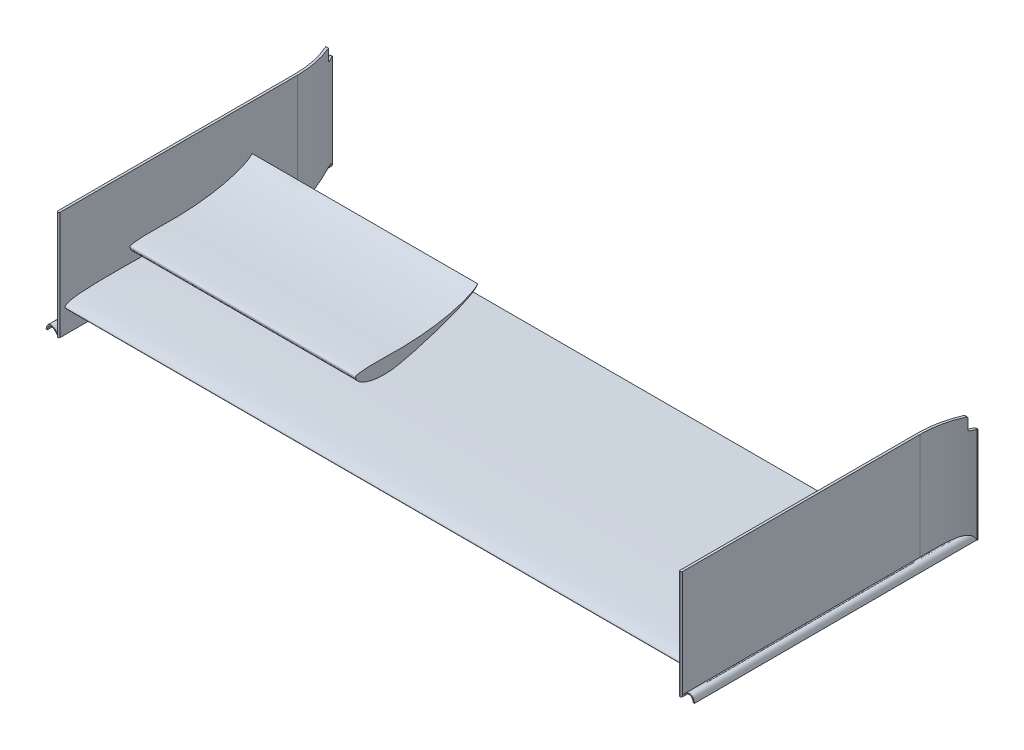
SolidWorks part; units mm, degrees
other "Markup1"
sketch "Sketch8" plane through (689.61, 321.434, 0) normal (0.4886, 0.11, -0.8656) x (-0.8712, 0.0061, -0.491)
ref_plane "Front Plane" through (0, 0, 0) normal (0, 0, 1) x (1, 0, 0)
ref_plane "Top Plane" through (0, 0, 0) normal (0, 1, 0) x (1, 0, 0)
ref_plane "Center Plane" through (0, 0, 0) normal (1, 0, 0) x (0, 0, -1)
ref_plane "Front Limit" through (0, 0, 1702.0819) normal (0, 0, 1) x (1, 0, 0)
ref_plane "Right Limit" through (-711.2, 0, 0) normal (1, 0, 0) x (0, 0, -1)
ref_plane "Left Limit" through (711.2, 0, 0) normal (1, 0, 0) x (0, 0, -1)
ref_plane "Rear Limit Outside Inner Wheel Plane" through (0, 0, 1077.0819) normal (0, 0, 1) x (1, 0, 0)
ref_plane "Lower Limit" through (0, 0, 0) normal (0, 1, 0) x (1, 0, 0)
ref_plane "Upper Limit Outside Inner Wheel Plane" through (0, 250, 0) normal (0, 1, 0) x (1, 0, 0)
ref_plane "Right Tower Outer Limit" through (-502.92, 0, 0) normal (1, 0, 0) x (0, 0, -1)
ref_plane "Left Tower Outer Limit" through (502.92, 0, 0) normal (1, 0, 0) x (0, 0, -1)
ref_plane "Upper Limit" through (0, 500, 0) normal (0, 1, 0) x (1, 0, 0)
ref_plane "Wing Right Edge" through (-676.91, 0, 0) normal (1, 0, 0) x (0, 0, -1)
ref_plane "Endplate Clearance" through (0, 12.7, 0) normal (0, 1, 0) x (1, 0, 0)
ref_plane "Tower Left Edge" through (-285.75, 0, 0) normal (1, 0, 0) x (0, 0, -1)
ref_plane "Tower Right Edge" through (-479.552, 0, 0) normal (1, 0, 0) x (0, 0, -1)
ref_plane "Tower Mid-Plane" through (-382.651, 0, 0) normal (1, 0, 0) x (0, 0, -1)
sketch "Sketch13" plane through (0, 12.7, 0) normal (0, 1, 0) x (1, 0, 0)
  line L0 (-681.749, -1702.0819) -> (-748.5505, -1702.0819) construction
  line L3 (-338.2945, -1702.0819) -> (338.2945, -1702.0819) construction
  line L4 (-1656.8005, -1077.0819) -> (-1116.8551, -1077.0819) construction
  line L5 (-339.8221, -1077.0819) -> (339.8221, -1077.0819) construction
  line L6 (-711.2, -238.9653) -> (-711.2, 238.9653) construction
  line L9 (1249.6701, -1702.0819) -> (1297.5169, -1702.0819) construction
  line L10 (-692.8302, -1081.9916) -> (-688.3642, -1079.5705) construction
  line L11 (-704.7698, 2304.2869) -> (-704.7698, 1682.8955) construction
  line L12 (-698.5, -2427.286) -> (-698.5, -1932.9922) construction
  line L13 (-711.2, 1331.8621) -> (-711.2, 2114.8601) construction
  line L14 (-663.1866, -1178.8382) -> (-663.1866, -1686.8457)
  line L15 (-668.2666, -1686.8382) -> (-668.2666, -1178.8382)
  arc A6 (-663.1866, -1686.8457) -> (-668.2666, -1686.8382) centre (-665.7266, -1686.8419) cw
  arc A7 (-668.2666, -1178.8382) -> (-692.8302, -1081.9916) centre (-871.4666, -1178.8382) ccw
  arc A8 (-663.1866, -1178.8382) -> (-688.3642, -1079.5705) centre (-871.4666, -1178.8382) ccw
  arc A9 (-668.2666, -1178.8382) -> (-675.6742, -1124.4731) centre (-871.4666, -1178.8382) ccw construction
  arc A12 (-663.1866, -1178.8382) -> (-670.7794, -1123.114) centre (-871.4666, -1178.8382) ccw construction
  arc A13 (-688.3642, -1079.5705) -> (-692.8302, -1081.9916) centre (-690.5972, -1080.781) ccw
  point P7 (-665.7303, -1689.3819)
  point P8 (-698.5, -1702.0819)
  point P10 (-681.749, -1702.0819)
  point P17 (-704.85, -1089.7819)
  point P32 (-692.8302, -1081.9916)
  dimension "D5" = 2.54
  dimension "D9" = 203.2
  dimension "D1" = 12.7
  dimension "D3" = 12.7
  dimension "D4" = 5.08
  dimension "D6" = 508
  dimension "D8" = 60.4668
  dimension "D7" = 5.08
ref_plane "Right Tower Outer Edge" through (-496.57, 0, 0) normal (1, 0, 0) x (0, 0, -1)
ref_plane "Footplate Front Plane" through (0, 0, 1686.8419) normal (0, 0, 1) x (1, 0, 0)
extrude "Endplate" add sketch "Sketch13" along normal offset from surface (232.22 mm away) 5.08 contours L14 A6 L15 A7 A13 A8 up to plane "Upper Limit Outside Inner Wheel Plane"
sketch "Sketch9" plane through (0, 0, 0) normal (1, 0, 0) x (0, 0, -1)
  line L0 (-1689.3819, 6.2912) -> (-1689.3819, -13.0537) construction
  line L2 (423.3132, 0) -> (-423.3132, 0) construction
  line L3 (-1219.5516, 71.4792) -> (-1219.5392, 70.7113)
  line L4 (-1689.3819, 101.5557) -> (-1689.3819, 173.1029) construction
  line L5 (-1945.3823, 0) -> (-1740.2495, 0) construction
  line L10 (-1219.5516, 71.4792) -> (-1676.6819, 63.5) construction
  line L12 (-1676.6819, 63.5) -> (-1677.5512, 113.3019) construction
  spline S1 degree 3 poles (-1219.5392, 70.7113) (-1227.0861, 69.3984) (-1242.1864, 66.7717) (-1272.4544, 61.9112) (-1310.3806, 56.4182) (-1356, 50.7244) (-1401.7138, 45.9542) (-1447.5115, 42.2303) (-1493.4584, 39.5613) (-1531.8694, 38.8064) (-1562.6614, 39.5041) (-1585.7469, 40.7463) (-1608.8067, 42.8266) (-1627.9542, 45.4527) (-1643.2157, 48.362) (-1654.6407, 50.922) (-1664.1956, 54.4343) (-1671.8661, 57.2292) (-1679.7108, 64.0181) (-1670.8486, 69.3187) (-1662.9781, 71.2102) (-1653.0354, 72.9214) (-1641.5607, 74.0215) (-1626.2817, 75.0131) (-1607.2992, 75.6384) (-1584.5621, 75.8826) (-1561.8863, 75.857) (-1531.6907, 75.6204) (-1493.8655, 75.2452) (-1448.3868, 74.7043) (-1402.7761, 73.923) (-1357.1, 73.1795) (-1311.3437, 72.5052) (-1273.1582, 72.0528) (-1242.5505, 71.714) (-1227.2239, 71.5576) (-1219.5516, 71.4792) knots 0 0 0 0 0.02488 0.049781 0.099567 0.14934 0.199092 0.248839 0.298568 0.348561 0.373567 0.398591 0.423638 0.448742 0.461353 0.474029 0.486955 0.493558 0.502381 0.511191 0.517824 0.530564 0.54309 0.555505 0.580209 0.604805 0.629344 0.653862 0.702881 0.752206 0.801586 0.851045 0.900581 0.950217 0.975079 1 1 1 1
  dimension "D1" = 25.4
  dimension "D2" = 1
  dimension "D3" = 63.5
  dimension "D6" = 457.2
extrude "Boss-Extrude1" add sketch "Sketch9" against normal up to next contours S1 L3
ref_plane "Plane3" through (-2.4764, 0, 1687.8151) normal (-0.0015, 0, 1) x (1, 0, 0.0015)
sketch "Sketch10" plane through (-496.57, 0, 0) normal (1, 0, 0) x (0, 0, -1)
  line L7 (-1253.0024, 45.6286) -> (-1162.2541, 41.8604) construction
  line L15 (-1451.2356, 51.0549) -> (-1480.3015, 75.0777)
  line L16 (-1354.4791, 51.0549) -> (-1451.2356, 51.0549)
  line L19 (-1253.0024, 45.6286) -> (-1354.4791, 51.0549)
  line L21 (-1075.0863, 331.2535) -> (-1041.2474, 331.2535)
  line L24 (-1162.2541, 41.8604) -> (-1108.1928, 92.3259) construction
  line L25 (-1108.1928, 92.3259) -> (-1073.6675, 134.2437) construction
  line L26 (-1073.6675, 134.2437) -> (-1063.3396, 228.2149) construction
  line L27 (-1063.3396, 228.2149) -> (-1031.4549, 293.1063) construction
  line L28 (423.3132, 0) -> (-423.3132, 0) construction
  line L29 (-1077.0819, 339.8221) -> (-1077.0819, -339.8221) construction
  line L30 (-1219.5516, 71.4792) -> (-1219.5516, -47.0525) construction
  line L31 (-1688.4184, 71.4792) -> (-1416.5181, 71.4792) construction
  line L32 (-1219.5392, 70.7113) -> (-1219.5516, 71.4792)
  line L33 (-1219.5392, 70.7113) -> (-1219.5516, 71.4792)
  line L34 (-1038.7074, 299.3065) -> (-1038.7074, 328.7135)
  line L35 (-1036.1674, 296.7665) -> (-1033.7345, 296.7665)
  line L37 (-1178.8382, 244.92) -> (-1686.8457, 244.92) construction
  line L38 (-1075.0863, 331.2535) -> (-1097.159, 330.9939)
  circle A11 centre (-798.8819, 203.2) radius 203.2 construction
  arc A14 (-1036.1674, 296.7665) -> (-1038.7074, 299.3065) centre (-1036.1674, 299.3065) cw
  arc A15 (-1031.4549, 293.1063) -> (-1033.7345, 296.7665) centre (-1033.7345, 294.2265) ccw
  arc A16 (-1041.2474, 331.2535) -> (-1038.7074, 328.7135) centre (-1041.2474, 328.7135) cw
  spline_without_curve S0
  spline S1 degree 3 poles (-1097.159, 330.9939) (-1148.9166, 330.128) (-1194.764, 314.059) (-1331.7956, 204.3697) (-1393.3764, 127.2338) (-1480.3015, 75.0777) knots 0 0 0 0 0.231496 0.433154 1 1 1 1
  spline S3 degree 3 poles (-1219.5392, 70.7113) (-1227.0861, 69.3984) (-1242.1864, 66.7717) (-1272.4544, 61.9112) (-1310.3806, 56.4182) (-1356, 50.7244) (-1401.7138, 45.9542) (-1447.5115, 42.2303) (-1493.4584, 39.5613) (-1531.8694, 38.8064) (-1562.6614, 39.5041) (-1585.7469, 40.7463) (-1608.8067, 42.8266) (-1627.9542, 45.4527) (-1643.2157, 48.362) (-1654.6407, 50.922) (-1664.1956, 54.4343) (-1671.8661, 57.2292) (-1679.7108, 64.0181) (-1670.8486, 69.3187) (-1662.9781, 71.2102) (-1653.0354, 72.9214) (-1641.5607, 74.0215) (-1626.2817, 75.0131) (-1607.2992, 75.6384) (-1584.5621, 75.8826) (-1561.8863, 75.857) (-1531.6907, 75.6204) (-1493.8655, 75.2452) (-1448.3868, 74.7043) (-1402.7761, 73.923) (-1357.1, 73.1795) (-1311.3437, 72.5052) (-1273.1582, 72.0528) (-1242.5505, 71.714) (-1227.2239, 71.5576) (-1219.5516, 71.4792) knots 0 0 0 0 0.02488 0.049781 0.099567 0.14934 0.199092 0.248839 0.298568 0.348561 0.373567 0.398591 0.423638 0.448742 0.461353 0.474029 0.486955 0.493558 0.502381 0.511191 0.517824 0.530564 0.54309 0.555505 0.580209 0.604805 0.629344 0.653862 0.702881 0.752206 0.801586 0.851045 0.900581 0.950217 0.975079 1 1 1 1 construction
  spline S4 degree 3 poles (698.5236, -1924.2144) (65.8834, 81.8124) (-596.1286, 64.5596) (-1273.1582, 72.0528) (-1311.3437, 72.5052) (-1357.1, 73.1795) (-1402.7761, 73.923) (-1448.3868, 74.7043) (-1493.8655, 75.2452) (-1531.6907, 75.6204) (-1561.8863, 75.857) (-1584.5621, 75.8826) (-1607.2992, 75.6384) (-1626.2817, 75.0131) (-1641.5607, 74.0215) (-1653.0354, 72.9214) (-1662.9781, 71.2102) (-1670.8486, 69.3187) (-1679.7108, 64.0181) (-1671.8661, 57.2292) (-1664.1956, 54.4343) (-1654.6407, 50.922) (-1643.2157, 48.362) (-1627.9542, 45.4527) (-1608.8067, 42.8266) (-1585.7469, 40.7463) (-1562.6614, 39.5041) (-1531.8694, 38.8064) (-1493.4584, 39.5613) (-1447.5115, 42.2303) (-1401.7138, 45.9542) (-1356, 50.7244) (-1310.3806, 56.4182) (-1272.4544, 61.9112) (-952.6642, 113.2634) (-661.4362, 241.8766) (111.3217, -2533.5152) knots -2.09969 -2.09969 -2.09969 -2.09969 0.024921 0.049783 0.099419 0.148955 0.198414 0.247794 0.297119 0.346138 0.370656 0.395195 0.419791 0.444495 0.45691 0.469436 0.482176 0.488809 0.497619 0.506442 0.513045 0.525971 0.538647 0.551258 0.576362 0.601409 0.626433 0.651439 0.701432 0.751161 0.800908 0.85066 0.900433 0.950219 0.97512 1.952384 1.952384 1.952384 1.952384 only from (-1219.5516, 71.4792) to (-1219.5392, 70.7113)
  spline S5 degree 3 poles (-1219.5516, 71.4792) (-1227.2239, 71.5576) (-1242.5505, 71.714) (-1273.1582, 72.0528) (-1311.3437, 72.5052) (-1357.1, 73.1795) (-1402.7761, 73.923) (-1448.3868, 74.7043) (-1493.8655, 75.2452) (-1531.6907, 75.6204) (-1561.8863, 75.857) (-1584.5621, 75.8826) (-1607.2992, 75.6384) (-1626.2817, 75.0131) (-1641.5607, 74.0215) (-1653.0354, 72.9214) (-1662.9781, 71.2102) (-1670.8486, 69.3187) (-1679.7108, 64.0181) (-1671.8661, 57.2292) (-1664.1956, 54.4343) (-1654.6407, 50.922) (-1643.2157, 48.362) (-1627.9542, 45.4527) (-1608.8067, 42.8266) (-1585.7469, 40.7463) (-1562.6614, 39.5041) (-1531.8694, 38.8064) (-1493.4584, 39.5613) (-1447.5115, 42.2303) (-1401.7138, 45.9542) (-1356, 50.7244) (-1310.3806, 56.4182) (-1272.4544, 61.9112) (-1242.1864, 66.7717) (-1227.0861, 69.3984) (-1219.5392, 70.7113) knots 0 0 0 0 0.024921 0.049783 0.099419 0.148955 0.198414 0.247794 0.297119 0.346138 0.370656 0.395195 0.419791 0.444495 0.45691 0.469436 0.482176 0.488809 0.497619 0.506442 0.513045 0.525971 0.538647 0.551258 0.576362 0.601409 0.626433 0.651439 0.701432 0.751161 0.800908 0.85066 0.900433 0.950219 0.97512 1 1 1 1 construction
  point P0 (-901.0423, 453.0659)
  point P1 (-1057.5185, 453.0659)
  point P6 (-1172.7675, 276.2638)
  point P49 (-1213.8243, 119.2502)
  dimension "D3" = 406.4
  dimension "D4" = 278.2
  dimension "D1" = 2.54
  dimension "D6" = 2.54
  dimension "D7" = 2.54
  dimension "D5" = 0
sketch "Sketch29" plane through (-2.4764, 0, 1687.8151) normal (-0.0015, 0, 1) x (1, 0, 0.0015)
  line L0 (-691.2419, 13.171) -> (-688.7459, 12.7)
  line L1 (-663.8777, 14.3707) -> (-665.7909, 12.7)
  line L2 (-691.2419, 244.92) -> (-691.2419, 12.7) construction
  line L3 (-691.2419, 12.7) -> (-666.5362, 12.7) construction
  spline S0 degree 2 poles (-665.7909, 12.7) (-684.6668, 34.3152) (-688.7459, 12.7) knots 0 0 0 1 1 1
  spline S1 degree 1 poles (-663.8777, 14.3707) (-691.2419, 13.171) knots 0 0 1 1 construction
  spline S2 degree 2 poles (-663.8777, 14.3707) (-667.5007, 18.5279) (-672.8595, 23.0348) (-676.4087, 25.0689) (-678.9321, 25.8712) (-680.9696, 26.1076) (-682.991, 25.8639) (-684.8805, 25.1037) (-686.5179, 23.8905) (-688.2115, 21.9339) (-690.4596, 17.446) (-691.2419, 13.171) knots 0 0 0 0.1875 0.3125 0.40625 0.46875 0.53125 0.59375 0.65625 0.71875 0.8125 1 1 1
  dimension "D1" = 2.54
extrude "Boss-Extrude8" add sketch "Sketch29" against normal up to body
sketch "Sketch30" plane through (-2.4764, 0, 1687.8151) normal (-0.0015, 0, 1) x (1, 0, 0.0015)
  line L0 (-688.7459, 12.7) -> (-665.7909, 12.7)
  parabola Q0 (-688.7459, 12.7) -> (-665.7909, 12.7) focus (-681.9012, 20.7799) apex (-682.7369, 23.2216) construction
  parabola Q1 (-688.7459, 12.7) -> (-665.7909, 12.7) focus (-681.9012, 20.7799) apex (-682.7369, 23.2216) construction
  parabola Q2 (-688.7459, 12.7) -> (-665.7909, 12.7) focus (-681.9012, 20.7799) apex (-682.7369, 23.2216) construction
  spline S0 degree 2 poles (-688.7459, 12.7) (-682.9378, 35.0777) (-665.7909, 12.7) knots 0 0 0 1 1 1
extrude "Cut-Extrude1" cut sketch "Sketch30" against normal through all separate body
mirror "Mirror2" about plane through (0, 0, 0) normal (1, 0, 0) of bodies 141 120 117
move or copy body "Body-Move/Copy1" bodies to move or copy 121 copy no translate (0, -322.326, 19.8438) parameters "D1"=0, "D2"=322.326, "D3"=19.8438
ref_plane "Endplate Edge" through (-663.1866, 0, 0) normal (1, 0, 0) x (0, 0, -1)
curve "Curve1"
  spline degree 3 poles (0, -0.6596, 253.0171) (0, 0.164, 254.2303) (0, -0.6286, 253.1665) (0, -1.3215, 252.4604) (0, -2.7687, 250.8924) (0, -4.3082, 249.0425) (0, -5.8603, 246.5121) (0, -7.3644, 243.3654) (0, -8.9341, 239.5667) (0, -10.5476, 235.1217) (0, -12.1934, 230.0511) (0, -13.8573, 224.3813) (0, -15.5314, 218.144) (0, -17.2004, 211.3736) (0, -18.8523, 204.109) (0, -20.4766, 196.3935) (0, -22.065, 188.2741) (0, -23.5981, 179.7984) (0, -25.0735, 171.0197) (0, -26.4724, 161.9885) (0, -27.7973, 152.7634) (0, -29.0379, 143.4034) (0, -30.1902, 133.9763) (0, -31.2623, 124.5575) (0, -32.2271, 115.225) (0, -33.0667, 106.0547) (0, -33.7337, 97.1112) (0, -34.1925, 88.4456) (0, -34.3907, 80.1061) (0, -34.3696, 72.1354) (0, -33.9793, 64.5483) (0, -33.1884, 57.342) (0, -32.0701, 50.4871) (0, -30.6214, 43.9819) (0, -28.9226, 37.8331) (0, -27.0037, 32.0668) (0, -24.9097, 26.7074) (0, -22.6517, 21.7883) (0, -20.2757, 17.3253) (0, -17.8086, 13.3426) (0, -15.2839, 9.8652) (0, -12.755, 6.8945) (0, -10.1944, 4.4736) (0, -7.6243, 2.6141) (0, -5.1239, 1.2405) (0, -2.7499, 0.3601) (0, -0.5587, -0.0593) (0, 1.2945, 0.0216) (0, 2.9943, 0.4988) (0, 3.838, 2.2723) (0, 3.9564, 4.6569) (0, 4.0711, 7.9189) (0, 3.8942, 12.0212) (0, 3.5691, 16.9173) (0, 3.0484, 22.5528) (0, 2.3439, 28.87) (0, 1.4404, 35.838) (0, 0.1776, 43.4536) (0, -1.4059, 51.7537) (0, -3.1293, 60.7798) (0, -4.9489, 70.4879) (0, -6.7893, 80.817) (0, -8.5813, 91.6912) (0, -10.2652, 103.0261) (0, -11.7791, 114.724) (0, -13.079, 126.6798) (0, -14.1065, 138.7806) (0, -14.8349, 150.9048) (0, -15.2353, 162.9259) (0, -15.2859, 174.7134) (0, -14.9832, 186.1357) (0, -14.3342, 197.0622) (0, -13.3475, 207.3615) (0, -12.0608, 216.9108) (0, -10.5115, 225.5859) (0, -8.7514, 233.285) (0, -6.8681, 239.8664) (0, -4.8581, 245.2525) (0, -3.0186, 249.0954) (0, -1.3178, 251.9287) (0, -0.6596, 253.0171) (0, 0.164, 254.2303) (0, -0.6286, 253.1665) knots -0.009748 -0.004147 -0.001 0 0.00098 0.003649 0.007483 0.012095 0.017526 0.024052 0.031783 0.040678 0.05071 0.061833 0.073989 0.087118 0.101145 0.115991 0.13157 0.147788 0.164551 0.181758 0.199312 0.217095 0.23499 0.252857 0.270541 0.287887 0.304773 0.321101 0.336806 0.3518 0.366031 0.379616 0.392653 0.40517 0.417172 0.428604 0.439419 0.449597 0.459102 0.467908 0.475988 0.483309 0.489875 0.495803 0.501149 0.505903 0.510047 0.513579 0.516447 0.51935 0.523823 0.529974 0.537716 0.546968 0.557637 0.56962 0.582804 0.597247 0.613135 0.630444 0.649056 0.668822 0.689595 0.71119 0.733427 0.756094 0.778989 0.80189 0.824567 0.846792 0.868338 0.888978 0.908492 0.926659 0.943286 0.958169 0.971136 0.981956 0.990252 0.995853 0.999 1 1.00098 1.003649 1.007483 periodic
sketch "Sketch32" plane through (-663.1866, 0, 2912.7328) normal (-1, 0, 0) x (0, 0, 1)
  spline S1 degree 3 poles (-1615.8911, -175.0963) (-1616.9955, -174.0392) (-1616.0394, -175.0385) (-1615.4336, -175.8733) (-1614.0726, -177.633) (-1612.4379, -179.5365) (-1610.1057, -181.5709) (-1607.1317, -183.6629) (-1603.4987, -185.9355) (-1599.2088, -188.3651) (-1594.2815, -190.9365) (-1588.7412, -193.6303) (-1582.6193, -196.4332) (-1575.9486, -199.3232) (-1568.7667, -202.2812) (-1561.1165, -205.2892) (-1553.045, -208.3303) (-1544.5974, -211.3763) (-1535.8284, -214.4156) (-1526.7866, -217.42) (-1517.5326, -220.382) (-1508.1253, -223.2807) (-1498.6337, -226.1002) (-1489.1367, -228.8359) (-1479.7098, -231.4463) (-1470.4279, -233.8998) (-1461.3494, -236.1366) (-1452.5203, -238.1112) (-1443.9813, -239.7612) (-1435.7834, -241.1219) (-1427.9159, -242.0365) (-1420.3703, -242.4732) (-1413.1292, -242.5124) (-1406.1903, -242.1512) (-1399.5745, -241.4711) (-1393.3137, -240.4985) (-1387.4409, -239.2752) (-1381.9923, -237.8071) (-1376.992, -236.1384) (-1372.4697, -234.2929) (-1368.4569, -232.3004) (-1364.9644, -230.2159) (-1362.0315, -228.0033) (-1359.6741, -225.6836) (-1357.8283, -223.3514) (-1356.5116, -221.0635) (-1355.7003, -218.8836) (-1355.4622, -216.9643) (-1355.6579, -215.1342) (-1357.3348, -213.9592) (-1359.7657, -213.4239) (-1363.0994, -212.7402) (-1367.3474, -212.2106) (-1372.4372, -211.6957) (-1378.321, -211.2537) (-1384.9375, -210.8824) (-1392.2577, -210.6028) (-1400.3058, -210.5802) (-1409.1132, -210.7686) (-1418.6914, -210.9749) (-1428.9873, -211.1619) (-1439.9252, -211.2625) (-1451.4151, -211.2189) (-1463.3599, -210.9841) (-1475.6485, -210.5117) (-1488.165, -209.7746) (-1500.7833, -208.7323) (-1513.3738, -207.3784) (-1525.8014, -205.7052) (-1537.9282, -203.7129) (-1549.6184, -201.4207) (-1560.7388, -198.8586) (-1571.1557, -196.058) (-1580.7496, -193.0791) (-1589.3993, -189.9818) (-1597.0091, -186.8372) (-1603.4484, -183.7596) (-1608.637, -180.7591) (-1612.2686, -178.2016) (-1614.8863, -175.9617) (-1615.8911, -175.0963) (-1616.9955, -174.0392) (-1616.0394, -175.0385) knots -0.009748 -0.004147 -0.001 0 0.00098 0.003649 0.007483 0.012095 0.017526 0.024052 0.031783 0.040678 0.05071 0.061833 0.073989 0.087118 0.101145 0.115991 0.13157 0.147788 0.164551 0.181758 0.199312 0.217095 0.23499 0.252857 0.270541 0.287887 0.304773 0.321101 0.336806 0.3518 0.366031 0.379616 0.392653 0.40517 0.417172 0.428604 0.439419 0.449597 0.459102 0.467908 0.475988 0.483309 0.489875 0.495803 0.501149 0.505903 0.510047 0.513579 0.516447 0.51935 0.523823 0.529974 0.537716 0.546968 0.557637 0.56962 0.582804 0.597247 0.613135 0.630444 0.649056 0.668822 0.689595 0.71119 0.733427 0.756094 0.778989 0.80189 0.824567 0.846792 0.868338 0.888978 0.908492 0.926659 0.943286 0.958169 0.971136 0.981956 0.990252 0.995853 0.999 1 1.00098 1.003649 1.007483 only from (-1616.7872, -174.2477) to (-1616.7872, -174.2477)
  point P0 (-1531.0038, -84.375)
sketch "Sketch35" plane through (-663.1866, 0, 0) normal (1, 0, 0) x (0, 0, -1)
  line L0 (-1114.6887, -79.5331) -> (-1114.6887, -102.0276)
  line L1 (-1112.1487, -104.5676) -> (-1100.6169, -104.5676)
  line L5 (-1117.2287, -76.9931) -> (-1134.0615, -76.9931)
  line L6 (-1098.0769, -107.1076) -> (-1098.0769, -118.299)
  line L7 (-1098.0769, -118.299) -> (-1081.2177, -118.299)
  line L8 (-1081.2177, -118.299) -> (-1081.2177, -76.9931)
  line L9 (-1081.2177, -76.9931) -> (-1081.2177, -62.3541)
  line L10 (-1081.2177, -62.3541) -> (-1134.0615, -62.3541)
  line L11 (-1134.0615, -62.3541) -> (-1134.0615, -76.9931)
  arc A0 (-1114.6887, -102.0276) -> (-1112.1487, -104.5676) centre (-1112.1487, -102.0276) ccw
  arc A1 (-1117.2287, -76.9931) -> (-1114.6887, -79.5331) centre (-1117.2287, -79.5331) cw
  arc A2 (-1100.6169, -104.5676) -> (-1098.0769, -107.1076) centre (-1100.6169, -107.1076) cw
  dimension "D1" = 2.54
  dimension "D2" = 2.54
  dimension "D3" = 2.54
ref_plane "Plane5" through (660.6466, 0, 0) normal (-1, 0, 0) x (0, 0, 1)
sketch "Sketch40" plane through (663.1866, 0, 0) normal (-1, 0, 0) x (0, 0, 1)
  line L0 (1081.2177, -62.3541) -> (1081.2177, -118.299)
  line L1 (1081.2177, -118.299) -> (1098.0769, -118.299)
  line L2 (1098.0769, -118.299) -> (1098.0769, -107.1076)
  line L3 (1100.6169, -104.5676) -> (1112.1487, -104.5676)
  line L4 (1114.6887, -79.5331) -> (1114.6887, -102.0276)
  line L5 (1117.2287, -76.9931) -> (1134.0615, -76.9931)
  line L6 (1134.0615, -76.9931) -> (1134.0615, -62.3541)
  line L7 (1134.0615, -62.3541) -> (1081.2177, -62.3541)
  arc A0 (1114.6887, -79.5331) -> (1117.2287, -76.9931) centre (1117.2287, -79.5331) cw
  arc A1 (1098.0769, -107.1076) -> (1100.6169, -104.5676) centre (1100.6169, -107.1076) cw
  arc A2 (1114.6887, -102.0276) -> (1112.1487, -104.5676) centre (1112.1487, -102.0276) cw
  dimension "D1" = 2.54
  dimension "D2" = 2.54
extrude "Cut-Extrude5" cut sketch "Sketch40" against normal up to surface (15.6289 mm away) up to face at (680.345, -189.713, 1141.3494)
extrude "Cut-Extrude6" cut sketch "Sketch35" against normal up to surface (15.6289 mm away) up to face at (-680.345, -189.713, 1141.3494)
ref_plane "Plane6" through (0, -325.12, 0) normal (0, 1, 0) x (1, 0, 0)
extrude "Boss-Extrude9" add sketch "Sketch32" against normal blind 482.6
